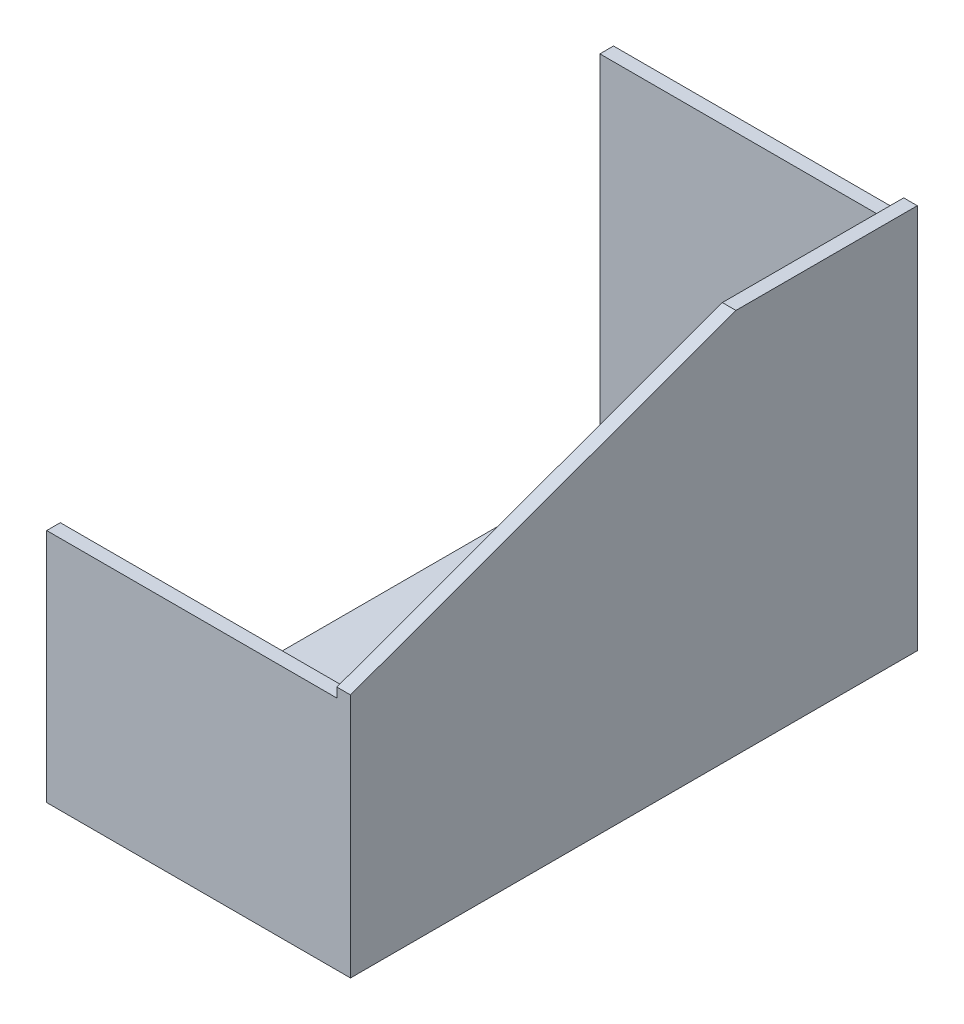
SolidWorks part; units mm, degrees
ref_plane "Спереди" through (0, 0, 0) normal (0, 0, 1) x (1, 0, 0)
ref_plane "Сверху" through (0, 0, 0) normal (0, 1, 0) x (1, 0, 0)
ref_plane "Справа" through (0, 0, 0) normal (1, 0, 0) x (0, 0, -1)
sketch "Эскиз18" plane through (0, 0, 0) normal (1, 0, 0) x (0, 0, -1)
  line L0 (53.75, 76) -> (53.75, -6)
  line L1 (53.75, -6) -> (-71.25, -6)
  line L2 (-71.25, -6) -> (-71.25, 45.9619)
  line L3 (-68.25, 45.9619) -> (-68.25, -3)
  line L4 (-68.25, -3) -> (50.75, -3)
  line L5 (50.75, -3) -> (50.75, 76)
  line L6 (50.75, 76) -> (53.75, 76)
  line L7 (-71.25, 45.9619) -> (-68.25, 45.9619)
  line L8 (50.75, -3) -> (50.75, -6) construction
  line L9 (-68.25, -3) -> (-68.25, -6) construction
  line L10 (-41.25, 0) -> (41.25, 0) construction
  line L11 (-41.25, 21) -> (-41.25, 3) construction
  line L12 (-71.25, 45.9619) -> (-68.25, 45.9619) construction
  dimension "D1" = 3
  dimension "D2" = 3
  dimension "D3" = 27
  dimension "D4" = 125
  dimension "D5" = 82
extrude "Бобышка-Вытянуть1" add sketch "Эскиз18" along normal mid plane 64
sketch "Эскиз19" plane through (32, 0, 0) normal (1, 0, 0) x (0, 0, -1)
  line L0 (-71.25, 48.0625) -> (13.75, 79)
  line L1 (13.75, 79) -> (53.75, 79)
  line L8 (53.75, 76) -> (50.75, 76)
  line L9 (50.75, 76) -> (50.75, -3)
  line L10 (50.75, -3) -> (-68.25, -3)
  line L11 (-68.25, -3) -> (-68.25, 45.9619)
  line L12 (-68.25, 45.9619) -> (-71.25, 45.9619)
  line L13 (-71.25, 45.9619) -> (-71.25, -6)
  line L14 (-71.25, -6) -> (53.75, -6)
  line L15 (53.75, -6) -> (53.75, 76)
  line L21 (-71.25, 48.0625) -> (-71.25, -6)
  line L22 (-71.25, -6) -> (53.75, -6)
  line L23 (53.75, -6) -> (53.75, 79)
  dimension "D1" = 0
extrude "Бобышка-Вытянуть2" add sketch "Эскиз19" along normal blind 3
